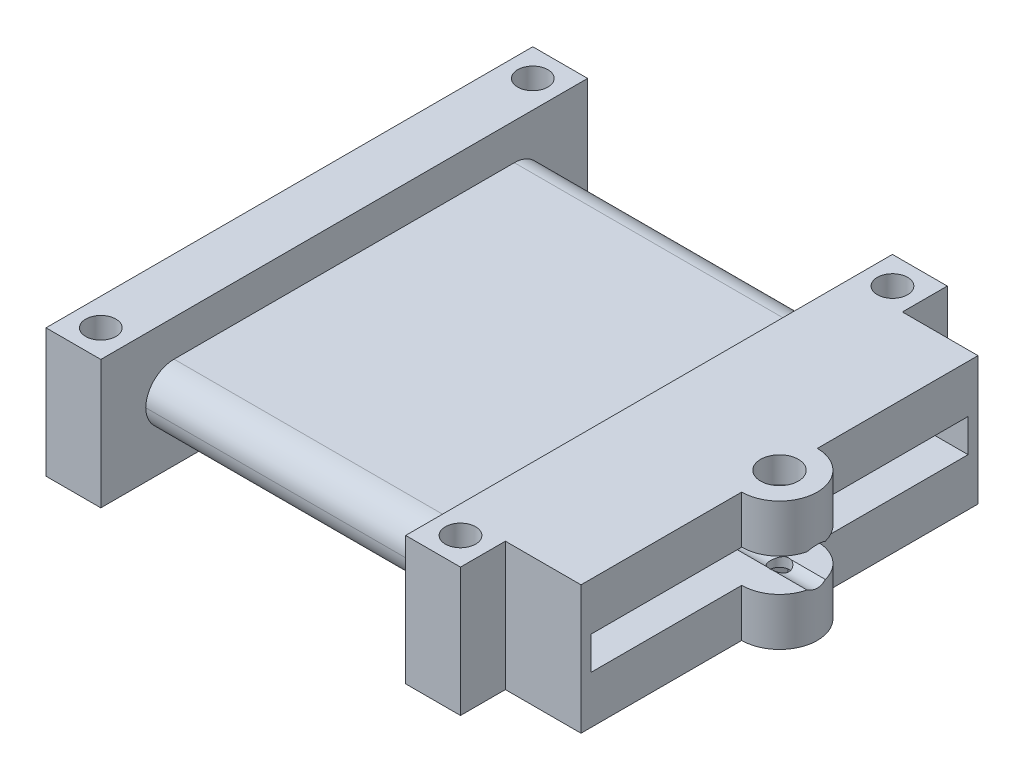
SolidWorks part; units mm, degrees
ref_plane "Front Plane" through (0, 0, 0) normal (0, 0, 1) x (1, 0, 0)
ref_plane "Top Plane" through (0, 0, 0) normal (0, 1, 0) x (1, 0, 0)
ref_plane "Right Plane" through (0, 0, 0) normal (1, 0, 0) x (0, 0, -1)
sketch "Sketch1" plane through (0, 0, 0) normal (1, 0, 0) x (0, 0, -1)
  line L0 (21, 5.9) -> (21, 0) construction
  line L1 (0, 0) -> (42, 0)
  line L2 (0, 0) -> (0, 5.9)
  line L3 (0, 5.9) -> (42, 5.9)
  line L4 (42, 0) -> (42, 5.9)
  line L6 (1.05, 1.2) -> (40.95, 1.2)
  line L7 (1.05, 1.2) -> (1.05, 4.7)
  line L8 (1.05, 4.7) -> (40.95, 4.7)
  line L9 (40.95, 1.2) -> (40.95, 4.7)
  line L10 (1.05, 1.2) -> (40.95, 4.7) construction
  line L11 (1.05, 4.7) -> (40.95, 1.2) construction
  point P7 (21, 2.95)
  dimension "D1" = 42
  dimension "D2" = 5.9
  dimension "D3" = 3.5
  dimension "D4" = 39.9
extrude "Boss-Extrude1" add sketch "Sketch1" along normal blind 32.25
fillet "Fillet2" radius 3 4 edges at (16.125, 0, -42) (16.125, 0, 0) (16.125, 5.9, 0) (16.125, 5.9, -42)
sketch "Sketch2" plane through (32.25, 0, 0) normal (1, 0, 0) x (0, 0, -1)
  line L0 (21, 5.9) -> (21, 0) construction
  line L1 (39, 5.9) -> (3, 5.9) construction
  line L2 (3, 0) -> (39, 0) construction
  line L4 (-4.75, -3.85) -> (46.75, -3.85)
  line L5 (-4.75, -3.85) -> (-4.75, 9.75)
  line L6 (-4.75, 9.75) -> (46.75, 9.75)
  line L7 (46.75, -3.85) -> (46.75, 9.75)
  line L8 (-4.75, -3.85) -> (46.75, 9.75) construction
  line L9 (-4.75, 9.75) -> (46.75, -3.85) construction
  line L14 (40.95, 1.2) -> (1.05, 1.2)
  line L15 (40.95, 1.2) -> (40.95, 4.7)
  line L16 (40.95, 4.7) -> (1.05, 4.7)
  line L17 (1.05, 1.2) -> (1.05, 4.7)
  line L18 (40.95, 1.2) -> (1.05, 4.7) construction
  line L19 (40.95, 4.7) -> (1.05, 1.2) construction
  point P6 (21, 2.95)
  point P11 (21, 2.95)
  point P12 (21, 2.95)
  dimension "D1" = 13.6
  dimension "D2" = 51.5
extrude "Boss-Extrude2" add sketch "Sketch2" along normal blind 5.8
sketch "Sketch3" plane through (0, 0, 0) normal (-1, 0, 0) x (0, 0, 1)
  line L0 (-21, 5.9) -> (-21, 0) construction
  line L1 (-39, 5.9) -> (-3, 5.9) construction
  line L2 (-3, 0) -> (-39, 0) construction
  line L4 (4.75, -3.85) -> (-46.75, -3.85)
  line L5 (4.75, -3.85) -> (4.75, 9.75)
  line L6 (4.75, 9.75) -> (-46.75, 9.75)
  line L7 (-46.75, -3.85) -> (-46.75, 9.75)
  line L8 (4.75, -3.85) -> (-46.75, 9.75) construction
  line L9 (4.75, 9.75) -> (-46.75, -3.85) construction
  line L10 (-1.05, 1.2) -> (-40.95, 1.2)
  line L11 (-1.05, 1.2) -> (-1.05, 4.7)
  line L12 (-1.05, 4.7) -> (-40.95, 4.7)
  line L13 (-40.95, 1.2) -> (-40.95, 4.7)
  line L14 (-1.05, 1.2) -> (-40.95, 4.7) construction
  line L15 (-1.05, 4.7) -> (-40.95, 1.2) construction
  point P6 (-21, 2.95)
  point P12 (-21, 2.95)
extrude "Boss-Extrude3" add sketch "Sketch3" along normal blind 5.8
sketch "Sketch4" plane through (0, 9.75, 0) normal (0, 1, 0) x (1, 0, 0)
  line L0 (-2.9, 46.75) -> (-2.9, 43.85) construction
  line L1 (-5.8, 46.75) -> (0, 46.75) construction
  line L2 (35.15, 46.75) -> (35.15, 43.85) construction
  line L3 (38.05, 46.75) -> (32.25, 46.75) construction
  line L4 (-2.9, -4.75) -> (-2.9, -1.85) construction
  line L5 (-5.8, -4.75) -> (0, -4.75) construction
  line L6 (35.15, -4.75) -> (35.15, -1.85) construction
  line L7 (38.05, -4.75) -> (32.25, -4.75) construction
  circle A0 centre (-2.9, 43.85) radius 1.6
  circle A1 centre (35.15, 43.85) radius 1.6
  circle A2 centre (-2.9, -1.85) radius 1.6
  circle A3 centre (35.15, -1.85) radius 1.6
  dimension "D2" = 3.2
  dimension "D4" = 3.2
  dimension "D6" = 3.2
  dimension "D8" = 3.2
  dimension "D1" = 2.9
  dimension "D3" = 2.9
  dimension "D5" = 2.9
  dimension "D7" = 2.9
extrude "Cut-Extrude1" cut sketch "Sketch4" against normal through all
sketch "Sketch6" plane through (38.05, 0, 0) normal (1, 0, 0) x (0, 0, -1)
  line L0 (46.75, -3.85) -> (46.75, 9.75) construction
  line L1 (-4.75, -3.85) -> (46.75, -3.85)
  line L2 (-4.75, -3.85) -> (-4.75, 3.35)
  line L3 (-4.75, 3.35) -> (46.75, 3.35)
  line L4 (46.75, -3.85) -> (46.75, 3.35)
  dimension "D1" = 7.2
extrude "Cut-Extrude2" [suppressed] cut sketch "Sketch6" against normal blind 5.8
sketch "Sketch7" plane through (-5.8, 0, 0) normal (-1, 0, 0) x (0, 0, 1)
  line L0 (4.75, -3.85) -> (4.75, 9.75) construction
  line L1 (-46.75, -3.85) -> (4.75, -3.85)
  line L2 (-46.75, -3.85) -> (-46.75, 3.35)
  line L3 (-46.75, 3.35) -> (4.75, 3.35)
  line L4 (4.75, -3.85) -> (4.75, 3.35)
  dimension "D1" = 7.2
extrude "Cut-Extrude3" [suppressed] cut sketch "Sketch7" against normal blind 5.8
sketch "Sketch8" plane through (0, 9.75, 0) normal (0, 1, 0) x (1, 0, 0)
  line L1 (0, 41.9996) -> (32.25, 41.9996) construction
  line L2 (38.05, 46.75) -> (38.05, -4.75) construction
  line L3 (46.05, 25) -> (46.05, 41.9996)
  line L4 (46.05, 41.9996) -> (38.05, 41.9996)
  line L5 (46.05, 17) -> (46.05, 0.0004)
  line L6 (46.05, 0.0004) -> (38.05, 0.0004)
  line L12 (-42.1211, 21) -> (79.5205, 21) construction
  line L13 (-5.8, -4.75) -> (-5.8, 46.75) construction
  circle A0 centre (46.05, 21) radius 4
  point P17 (-5.8, 21)
  line M5 (38.05, -4.75) -> (38.05, 46.75)
  dimension "D1" = 8
  dimension "D2" = 8
extrude "Boss-Extrude4" add sketch "Sketch8" against normal blind 13.6 contours A0 L3 L4 M5 | A0 L6 L5 M5 | A0 | A0 L12 region at (41.8639, 9.75, -32.2114) region at (46.05, 9.75, -22.6977) region at (46.05, 9.75, -19.3023) region at (41.8639, 9.75, -9.7886)
hole_wizard "CSK for M2 Flat Head Machine Screw1" positions "Sketch12" profile "Sketch13" countersink size "M2" standard "ANSI Metric" end condition through all
sketch "Sketch12" plane through (0, 9.75, 0) normal (0, 1, 0) x (1, 0, 0)
  point P0 (46.05, 21)
sketch "Sketch13" plane through (46.05, 9.75, -21) normal (1, 0, 0) x (0, 0, 1)
  line L0 (0, 0) -> (0, 13.6)
  line L1 (0, 13.6) -> (1, 13.6)
  line L2 (1, 13.6) -> (1, 3.75)
  line L3 (1, 3.75) -> (2, 2.75)
  line L4 (2, 2.75) -> (2, 0)
  line L6 (2, 0) -> (0, 0)
  line L7 (-1, 3.75) -> (-2, 2.75) construction
  line L11 (0, -6.35) -> (0, 107.95) construction
  dimension "Thru Hole Dia." = 2
  dimension "Thru Hole Depth" = 13.6
  dimension "C'Sink Dia." = 4
  dimension "C'Sink Angle" = 90
  dimension "Head Clearance" = 2.75
sketch "Sketch14" plane through (0, -3.85, 0) normal (0, -1, 0) x (1, 0, 0)
  line L1 (43.6251, -21) -> (44.8376, -23.1)
  line L2 (44.8376, -23.1) -> (47.2624, -23.1)
  line L3 (47.2624, -23.1) -> (48.4749, -21)
  line L4 (48.4749, -21) -> (47.2624, -18.9)
  line L5 (47.2624, -18.9) -> (44.8376, -18.9)
  line L6 (44.8376, -18.9) -> (43.6251, -21)
  circle A0 centre (46.05, -21) radius 2.1 construction
  point P1 (48.4749, -21)
  dimension "D1" = 4.2
extrude "Cut-Extrude4" cut sketch "Sketch14" against normal blind 4
sketch "Sketch15" plane through (-5.8, 0, 0) normal (-1, 0, 0) x (0, 0, 1)
  line L1 (-40.95, 1.2) -> (-1.05, 1.2)
  line L2 (-40.95, 1.2) -> (-40.95, 4.7)
  line L3 (-40.95, 4.7) -> (-1.05, 4.7)
  line L4 (-1.05, 1.2) -> (-1.05, 4.7)
  line L5 (-46.75, -3.85) -> (-40.95, -3.85)
  line L6 (-46.75, -3.85) -> (-46.75, -1.85)
  line L7 (-46.75, -1.85) -> (-40.95, -1.85)
  line L8 (-40.95, -3.85) -> (-40.95, -1.85)
  line L9 (4.75, -3.85) -> (-1.05, -3.85)
  line L10 (4.75, -3.85) -> (4.75, -1.85)
  line L11 (4.75, -1.85) -> (-1.05, -1.85)
  line L12 (-1.05, -3.85) -> (-1.05, -1.85)
  dimension "D1" = 5.8
  dimension "D2" = 2
  dimension "D3" = 5.8
  dimension "D4" = 2
extrude "Cut-Extrude5" cut sketch "Sketch15" against normal through all contours L2 L1 L4 L3
sketch "Sketch17" plane through (-5.8, 0, 0) normal (-1, 0, 0) x (0, 0, 1)
  line L0 (-21, 4.7) -> (-21, 1.2) construction
  line L1 (-1.05, 4.7) -> (-40.95, 4.7) construction
  line L2 (-40.95, 1.2) -> (-1.05, 1.2) construction
  circle A0 centre (-21, 2.95) radius 2
  dimension "D1" = 4
extrude "Cut-Extrude6" cut sketch "Sketch17" against normal through all
